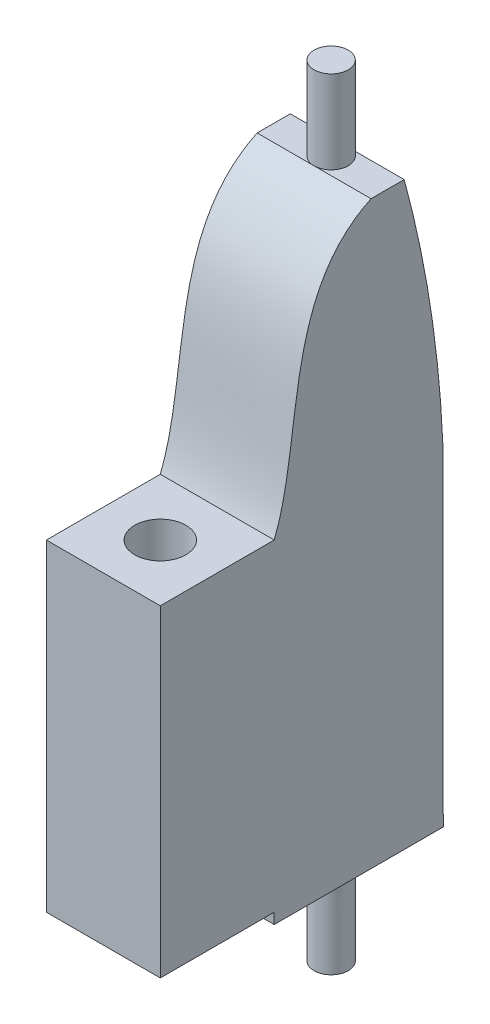
SolidWorks part; units mm, degrees
ref_plane "前视基准面" through (0, 0, 0) normal (0, 0, 1) x (1, 0, 0)
ref_plane "上视基准面" through (0, 0, 0) normal (0, 1, 0) x (1, 0, 0)
ref_plane "右视基准面" through (0, 0, 0) normal (1, 0, 0) x (0, 0, -1)
sketch "草图1" plane through (0, 0, 0) normal (0, 0, 1) x (1, 0, 0)
  line L0 (22.5, 0) -> (22.5, 287.3668) construction
  line L1 (0, 0) -> (16.5, 0)
  line L2 (0, 0) -> (0, 10)
  line L3 (0, 10) -> (16.5, 10)
  line L4 (16.5, 0) -> (16.5, 10)
  line L5 (16.5, 0) -> (28.5, 0)
  line L6 (16.5, 0) -> (16.5, 10)
  line L7 (16.5, 10) -> (28.5, 10)
  line L8 (28.5, 0) -> (28.5, 10)
  line L9 (28.5, 10) -> (45, 10)
  line L10 (28.5, 10) -> (28.5, 0)
  line L11 (28.5, 0) -> (45, 0)
  line L12 (45, 10) -> (45, 0)
  line L13 (0, 10) -> (1, 10)
  line L14 (0, 10) -> (0, 102)
  line L15 (0, 102) -> (1, 102)
  line L16 (1, 10) -> (1, 102)
  line L17 (1, 102) -> (44, 102)
  line L18 (1, 102) -> (1, 10)
  line L19 (1, 10) -> (44, 10)
  line L20 (44, 102) -> (44, 10)
  line L21 (44, 102) -> (45, 102)
  line L22 (44, 102) -> (44, 10)
  line L23 (44, 10) -> (45, 10)
  line L24 (45, 102) -> (45, 10)
  line L25 (0, 0) -> (-10, 0)
  line L26 (0, 0) -> (0, 250)
  line L27 (0, 250) -> (-10, 250)
  line L28 (-10, 0) -> (-10, 250)
  line L29 (45, 0) -> (55, 0)
  line L30 (45, 0) -> (45, 250)
  line L31 (45, 250) -> (55, 250)
  line L32 (55, 0) -> (55, 250)
  line L33 (-10, 250) -> (55, 250)
  line L34 (-10, 250) -> (-10, 260)
  line L35 (-10, 260) -> (55, 260)
  line L36 (55, 260) -> (55, 250)
  line L37 (-10, 250) -> (55, 250)
  line L46 (-27.5, 0) -> (72.5, 0)
  line L47 (147.5, 475.7809) -> (197.5, 475.7809)
  line L52 (147.5, 475.7809) -> (172.5, 475.7809)
  line L56 (72.5, 0) -> (-27.5, 0)
  line L57 (72.5, 0) -> (72.5, 250)
  line L58 (72.5, 250) -> (-27.5, 250)
  line L59 (-27.5, 0) -> (-27.5, 250)
  line L60 (-27.5, 0) -> (72.5, 0)
  line L61 (-27.5, 0) -> (-27.5, -33)
  line L62 (-27.5, -33) -> (72.5, -33)
  line L63 (72.5, 250) -> (72.5, 0)
  line L64 (72.5, 0) -> (72.5, -33)
  point P21 (22.5, 0)
  dimension "D1" = 16.5
  dimension "D2" = 12
  dimension "D3" = 16.5
  dimension "D4" = 10
  dimension "D5" = 1
  dimension "D6" = 43
  dimension "D7" = 92
  dimension "D8" = 10
  dimension "D9" = 250
  dimension "D10" = 10
  dimension "D11" = 250
  dimension "D12" = 10
  dimension "D13" = 50
  dimension "D16" = 33
revolve "旋转1" add sketch "草图1" angle 360 about L0 region at (8.25, 5, 0) region at (-5, 125, 0) region at (0.5, 56, 0) region at (36.75, 5, 0) region at (50, 125, 0) region at (44.5, 56, 0)
sketch "草图2" plane through (0, 0, 0) normal (0, -1, 0) x (1, 0, 0)
  line L0 (28.5, 0) -> (30.2, 0)
  line L1 (28.5, 2) -> (28.1569, 2)
  line L2 (28.5, 0) -> (30.2, 0)
  line L3 (28.5, 0) -> (28.5, 2)
  line L4 (28.5, 2) -> (30.2, 2)
  line L5 (30.2, 0) -> (30.2, 2)
  line L6 (28.5, 0) -> (30.2, 0)
  line L7 (28.5, 0) -> (28.5, -2)
  line L8 (28.5, -2) -> (30.2, -2)
  line L9 (30.2, 0) -> (30.2, -2)
  line L10 (28.1569, 2) -> (28.1569, -2)
  line L11 (28.1569, -2) -> (28.5, -2)
  circle A0 centre (22.5, 0) radius 6 construction
  circle M11 centre (22.5, 0) radius 6
  dimension "D1" = 1.7
  dimension "D2" = 2
  dimension "D3" = 2
extrude "切除-拉伸1" cut sketch "草图2" against normal blind 10 contours L9 L0 L7 L8 | L11 L7 M11 | L3 L1 M11 | L0 L5 L4 L3 region at (29.35, 0, 1) region at (28.3976, 0, 1.5029) region at (29.35, 0, -1) region at (28.3976, 0, -1.5029)
sketch "草图3" plane through (0, 250, 0) normal (0, 1, 0) x (1, 0, 0)
  line L0 (-27.5, 0) -> (72.5, 0) construction
  line L1 (-27.5, 0) -> (22.5, 0)
  line L4 (22.5, 0) -> (22.5, 32.5)
  line L5 (72.5, 0) -> (-27.5, 0) construction
  line L6 (72.5, 0) -> (-27.5, 0) construction
  line L8 (22.5, 32.5) -> (22.5, 0)
  line L9 (22.5, 0) -> (72.5, 0)
  line L12 (22.5, 0) -> (72.5, 0)
  line L13 (22.5, 0) -> (22.5, -32.5)
  line L17 (22.5, -32.5) -> (22.5, 0)
  line L18 (22.5, 0) -> (-27.5, 0)
  line L20 (22.5, 0) -> (-27.5, 0)
  line L21 (22.5, 0) -> (22.5, 50)
  line L22 (22.5, 50) -> (-27.5, 50)
  line L23 (-27.5, 0) -> (-27.5, 50)
  line L24 (22.5, 0) -> (72.5, 0)
  line L25 (22.5, 0) -> (22.5, -50)
  line L26 (22.5, -50) -> (72.5, -50)
  line L27 (72.5, 0) -> (72.5, -50)
  line L28 (-27.5, 50) -> (72.5, 50)
  line L29 (-27.5, 50) -> (-27.5, -50)
  line L30 (-27.5, -50) -> (72.5, -50)
  line L31 (72.5, 50) -> (72.5, -50)
  circle A0 centre (22.5, 0) radius 32.5 construction
  circle A1 centre (22.5, 0) radius 32.5
  circle A2 centre (22.5, 0) radius 50
  circle M1 centre (22.5, 0) radius 32.5
  dimension "D1" = 100
  dimension "D5" = 50
extrude "凸台-拉伸1" add sketch "草图3" against normal blind 250 contours L23 L1 M1 | L1 M1 | L27 L9 M1 | L9 M1 region at (-4.1544, 250, -26.6544) region at (-4.1544, 250, 26.6544) region at (49.1544, 250, -26.6544) region at (49.1544, 250, 26.6544)
extrude "凸台-拉伸7" add sketch "草图3<5>" against normal blind 250 contours A2 L26 L27 | A2 L29 L30 | A2 L31 L28 | A2 L22 L23 region at (-16.3316, 250, 38.8316) region at (-16.3316, 250, -38.8316) region at (61.3316, 250, -38.8316) region at (61.3316, 250, 38.8316)
sketch "草图3<5>" plane through (0, 250, 0) normal (0, 1, 0) x (1, 0, 0) same geometry as "草图3"
extrude "凸台-拉伸8" add sketch "草图1<21>" along normal blind 50 and the other way blind 50 contours L64 L46 L29 L11 L5 L1 L25 L61 L62 region at (22.5, -16.5, 0)
sketch "草图1<21>" plane through (0, 0, 0) normal (0, 0, 1) x (1, 0, 0) same geometry as "草图1"
sketch "草图5" plane through (0, -33, 0) normal (0, -1, 0) x (1, 0, 0)
  line L0 (-10, 0) -> (55, 0) construction
  line L1 (-27.5, 0) -> (72.5, 0)
  line L2 (22.5, -50) -> (22.5, 50)
  line L3 (-27.5, 0) -> (22.5, -50) construction
  line L4 (-27.5, 0) -> (22.5, 50) construction
  line L5 (22.5, -50) -> (72.5, 0) construction
  line L6 (22.5, 50) -> (72.5, 0) construction
  line L7 (-2.5, 25) -> (-6.9901, 29.4901)
  line L8 (-12.8553, 35.3553) -> (57.8553, -35.3553)
  line L9 (22.5, 50) -> (22.5, -50)
  line L10 (57.8553, 35.3553) -> (-12.8553, -35.3553)
  line L11 (72.5, 0) -> (-27.5, 0)
  line L12 (57.8553, -35.3553) -> (-12.8553, 35.3553)
  line L13 (22.5, -50) -> (22.5, 50)
  line L14 (-12.8553, -35.3553) -> (57.8553, 35.3553)
  circle A0 centre (22.5, 0) radius 50 construction
  circle A1 centre (-4.7451, 27.2451) radius 3.175 construction
  circle A2 centre (-4.7451, 27.2451) radius 4.77
  circle A3 centre (22.5, 38.5303) radius 4.77
  circle A4 centre (49.7451, 27.2451) radius 4.77
  circle A5 centre (61.0303, 0) radius 4.77
  circle A6 centre (49.7451, -27.2451) radius 4.77
  circle A7 centre (22.5, -38.5303) radius 4.77
  circle A8 centre (-4.7451, -27.2451) radius 4.77
  circle A9 centre (-16.0303, 0) radius 4.77
  point P43 (22.5, 0)
  dimension "D2" = 8
extrude "切除-拉伸2" cut sketch "草图5" against normal blind 9.525 contours L14 A8 | L14 A8 | L13 A7 | L13 A7 | L12 A6 | L12 A6 | L11 A5 | L11 A5 | L14 A4 | L14 A4 | L13 A3 | L13 A3 | L12 A2 L8 L7 | L8 A2 L12 L7 | L11 A9 | L11 A9 region at (-16.0303, -33, 2.0245) region at (-6.1766, -33, 25.8136) region at (-3.3136, -33, 28.6766) region at (20.4755, -33, 38.5303) region at (24.5245, -33, 38.5303) region at (48.3136, -33, 28.6766) region at (51.1766, -33, 25.8136) region at (61.0303, -33, 2.0245) region at (61.0303, -33, -2.0245) region at (51.1766, -33, -25.8136) region at (48.3136, -33, -28.6766) region at (24.5245, -33, -38.5303) region at (20.4755, -33, -38.5303) region at (-3.3136, -33, -28.6766) region at (-6.1766, -33, -25.8136) region at (-16.0303, -33, -2.0245)
sketch "草图7" plane through (0, -33, 0) normal (0, -1, 0) x (1, 0, 0)
  line L0 (4.9991, 22.4751) -> (4.9991, 32.0966)
  line L1 (49.7451, -27.2451) -> (44.9751, -27.2451) construction
  line L2 (49.7451, -27.2451) -> (49.7451, -22.4751) construction
  line L3 (49.7451, -22.4751) -> (44.9751, -22.4751) construction
  line L4 (44.9751, -27.2451) -> (44.9751, -22.4751) construction
  line L5 (-4.7451, 27.2451) -> (0.0249, 27.2451) construction
  line L6 (-4.7451, 27.2451) -> (-4.7451, 22.4751) construction
  line L7 (-4.7451, 22.4751) -> (0.0249, 22.4751) construction
  line L8 (0.0249, 27.2451) -> (0.0249, 22.4751) construction
  line L9 (0.0249, 22.4751) -> (44.9751, 22.4751)
  line L10 (0.0249, 22.4751) -> (0.0249, -22.4751)
  line L11 (0.0249, -22.4751) -> (44.9751, -22.4751)
  line L12 (44.9751, 22.4751) -> (44.9751, -22.4751)
  line L13 (4.9991, 22.4751) -> (41.7158, 22.4751)
  line L14 (4.9991, 32.0966) -> (41.7158, 32.0966)
  line L15 (41.7158, 22.4751) -> (41.7158, 32.0966)
  line L16 (44.9751, 17.2688) -> (54.6019, 17.2688)
  line L17 (44.9751, 17.2688) -> (44.9751, -15.9174)
  line L18 (54.6019, 17.2688) -> (54.6019, -15.9174)
  line L19 (44.9751, -15.9174) -> (54.6019, -15.9174)
  line L20 (41.7158, -22.4751) -> (41.7158, -31.6279)
  line L21 (41.7158, -22.4751) -> (4.1165, -22.4751)
  line L22 (41.7158, -31.6279) -> (4.1165, -31.6279)
  line L23 (4.1165, -22.4751) -> (4.1165, -31.6279)
  line L24 (0.0249, -14.5052) -> (-10.0052, -14.5052)
  line L25 (0.0249, -14.5052) -> (0.0249, 16.8275)
  line L26 (-10.0052, -14.5052) -> (-10.0052, 16.8275)
  line L27 (0.0249, 16.8275) -> (-10.0052, 16.8275)
  circle A0 centre (49.7451, -27.2451) radius 4.77 construction
  circle A1 centre (49.7451, -27.2451) radius 4.77 construction
  circle A2 centre (-4.7451, 27.2451) radius 4.77 construction
  circle A3 centre (-4.7451, 27.2451) radius 4.77 construction
  point P0 (44.9751, -27.2451)
  point P1 (49.7451, -22.4751)
  point P10 (-4.7451, 22.4751)
  point P11 (0.0249, 27.2451)
extrude "切除-拉伸5" cut sketch "草图7" against normal blind 33 contours L9 L15 L14 L0 | L10 L27 L26 L24 | L12 L9 L10 L11 | L11 L23 L22 L20 | L12 L19 L18 L16 region at (22.5, -33, 0) region at (23.3575, -33, 27.2859) region at (-4.9902, -33, 1.1611) region at (49.7885, -33, 0.6757) region at (22.9162, -33, -27.0515)
sketch "草图8" plane through (72.5, 0, 0) normal (1, 0, 0) x (0, 0, -1)
  line L0 (0, -33) -> (150, -33)
  line L1 (50, -33) -> (-50, -33) construction
  line L3 (150, -33) -> (135, -33)
  line L4 (150, -33) -> (150, 467)
  line L5 (150, 467) -> (135, 467)
  line L6 (135, -33) -> (135, 467)
  dimension "D1" = 150
  dimension "D2" = 15
  dimension "D3" = 500
sketch "草图9" plane through (0, 250, 0) normal (0, 1, 0) x (1, 0, 0)
sketch "草图10" plane through (0, 250, 0) normal (0, 1, 0) x (1, 0, 0)
  line L0 (72.5, 150) -> (72.5, 135) construction
  line L1 (22.5, 0) -> (72.5, 0) construction
  line L2 (22.5, 0) -> (22.5, 135) construction
  line L3 (22.5, 135) -> (72.5, 135) construction
  line L4 (72.5, 0) -> (72.5, 135) construction
sketch "草图12" plane through (0, 0, -50) normal (0, 0, -1) x (-1, 0, 0)
  line L0 (-72.5, -33) -> (-72.5, 467) construction
  line L1 (-72.5, 467) -> (27.5, 467)
  line L2 (-72.5, 467) -> (-72.5, -33)
  line L3 (-72.5, -33) -> (27.5, -33)
  line L4 (27.5, 467) -> (27.5, -33)
  line L5 (-72.5, -33) -> (-72.5, 467) construction
  line L6 (27.5, -33) -> (-72.5, -33) construction
  line L7 (27.5, -33) -> (27.5, 250) construction
extrude "凸台-拉伸10" add sketch "草图12" along normal blind 148
sketch "草图13" plane through (0, 467, 0) normal (0, 1, 0) x (1, 0, 0)
  line L0 (72.5, 150) -> (72.5, 135) construction
  line L1 (72.5, 150) -> (22.5, 150)
  line L2 (72.5, 150) -> (72.5, 135)
  line L3 (72.5, 135) -> (22.5, 135)
  line L4 (22.5, 150) -> (22.5, 135)
  circle A2 centre (22.5, 150) radius 15
extrude "凸台-拉伸12" add sketch "草图13" against normal blind 612 and the other way blind 73 contours L4 A2 L3 | L3 A2 L4 region at (28.8662, 467, -143.6338) region at (20.3779, 467, -152.1221)
sketch "草图15" plane through (0, 0, -198) normal (0, 0, -1) x (-1, 0, 0)
  line L0 (-72.5, -33) -> (-72.5, 467) construction
  line L1 (-22.5, 467) -> (-22.5, 578.0357)
  line L2 (27.5, 467) -> (-72.5, 467) construction
  line L3 (-22.5, 578.0357) -> (-22.5, 225.094)
  line L4 (-37.5, 467) -> (-72.5, 467)
  line L5 (-72.5, 467) -> (-72.5, 248.8087)
  line L6 (-7.5, 467) -> (27.5, 467)
  line L7 (27.5, 467) -> (27.5, 248.8087)
  spline S0 degree 3 poles (-37.5, 467) (-82.5811, 403.4849) (-64.3273, 320.5081) (-72.5, 248.8087) knots 0 0 0 0 1 1 1 1
  spline S1 degree 3 poles (-7.5, 467) (37.5811, 403.4849) (19.3273, 320.5081) (27.5, 248.8087) knots 0 0 0 0 1 1 1 1
sketch "草图14" plane through (72.5, 0, 0) normal (1, 0, 0) x (0, 0, -1)
  line L0 (198, 467) -> (198, -33) construction
  line L1 (198, 467) -> (50, 467) construction
  line L2 (50, 250) -> (50, 467)
  line L3 (50, 467) -> (135, 467)
  line L4 (164.1218, 467) -> (198, 467)
  line L5 (198, 467) -> (198, 250)
  spline S0 degree 3 poles (50, 250) (76.3156, 314.3966) (56.5596, 429.6801) (135, 467) knots 0 0 0 0 1 1 1 1
  spline S1 degree 2 poles (164.1218, 467) (193.0749, 360.4355) (198, 250) knots 0 0 0 1 1 1
  point P0 (135, 467)
  point P4 (198, 250)
  point P7 (164.1218, 467)
extrude "切除-拉伸4" cut sketch "草图14" against normal blind 239
sketch "草图16" plane through (0, -33, 0) normal (0, -1, 0) x (1, 0, 0)
  line L0 (-27.5, -50) -> (72.5, -50)
  line L1 (-27.5, -50) -> (-27.5, -198.7396)
  line L2 (72.5, -50) -> (72.5, -198.7396)
  line L3 (-27.5, -198.7396) -> (72.5, -198.7396)
extrude "凸台-拉伸15" add sketch "草图16" along normal blind 9.398
